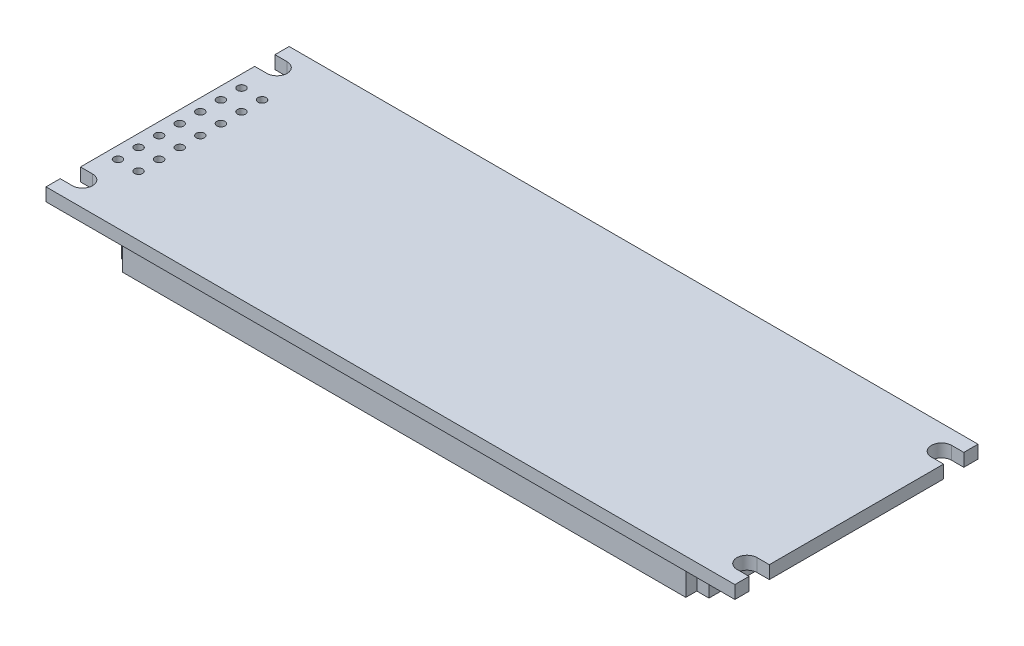
SolidWorks part; units mm, degrees
ref_plane "Plan de face" through (0, 0, 0) normal (0, 0, 1) x (1, 0, 0)
ref_plane "Plan de dessus" through (0, 0, 0) normal (0, 1, 0) x (1, 0, 0)
ref_plane "Plan de droite" through (0, 0, 0) normal (1, 0, 0) x (0, 0, -1)
sketch "Esquisse1" plane through (0, 0, 0) normal (0, 1, 0) x (1, 0, 0)
  line L0 (-41, -13.25) -> (-42.5, -13.25)
  line L1 (42.5, 15) -> (-42.5, 15)
  line L2 (-42.5, -10.75) -> (-42.5, 10.75)
  line L3 (42.5, -15) -> (-42.5, -15)
  line L4 (-42.5, -15) -> (-42.5, -13.25)
  line L5 (0, -15) -> (0, 15) construction
  line L6 (42.5, -15) -> (-42.5, 15) construction
  line L7 (-42.5, -10.75) -> (-41, -10.75)
  line L8 (-42.5, 0) -> (42.5, 0) construction
  line L10 (-42.5, 10.75) -> (-41, 10.75)
  line L11 (-42.5, 15) -> (-42.5, 13.25)
  line L12 (-41, 13.25) -> (-42.5, 13.25)
  line L13 (42.5, 15) -> (42.5, 13.25)
  line L14 (41, 13.25) -> (42.5, 13.25)
  line L15 (42.5, 10.75) -> (41, 10.75)
  line L16 (-42.5, 15) -> (42.5, -15) construction
  line L17 (42.5, -10.75) -> (41, -10.75)
  line L18 (42.5, -15) -> (42.5, -13.25)
  line L19 (41, -13.25) -> (42.5, -13.25)
  line L20 (42.5, -10.75) -> (42.5, 10.75)
  arc A0 (-41, -13.25) -> (-41, -10.75) centre (-41, -12) ccw
  arc A1 (-41, 13.25) -> (-41, 10.75) centre (-41, 12) cw
  arc A2 (41, 13.25) -> (41, 10.75) centre (41, 12) ccw
  arc A3 (41, -13.25) -> (41, -10.75) centre (41, -12) cw
  point P0 (0, 0)
  dimension "D1" = 85
  dimension "D3" = 82
  dimension "D5" = 1.25
  dimension "D2" = 30
  dimension "D4" = 24
extrude "Boss.-Extru.1" add sketch "Esquisse1" along normal blind 1.6 contours L19 L1 A1 L0 L3 L15 region at (0, 0, 0)
sketch "Esquisse2" plane through (0, 0, 0) normal (0, -1, 0) x (1, 0, 0)
  line L2 (42.5, 15) -> (-42.5, 15) construction
  line L3 (-42.5, 10.75) -> (-42.5, -10.75) construction
  circle A0 centre (-41, 7.62) radius 0.5
  circle A1 centre (-38.46, 7.62) radius 0.5
  circle A2 centre (-38.46, 5.08) radius 0.5
  circle A3 centre (-38.46, 2.54) radius 0.5
  circle A4 centre (-38.46, 0) radius 0.5
  circle A5 centre (-38.46, -2.54) radius 0.5
  circle A6 centre (-38.46, -5.08) radius 0.5
  circle A7 centre (-38.46, -7.62) radius 0.5
  circle A8 centre (-41, 5.08) radius 0.5
  circle A9 centre (-41, 2.54) radius 0.5
  circle A10 centre (-41, 0) radius 0.5
  circle A11 centre (-41, -2.54) radius 0.5
  circle A12 centre (-41, -5.08) radius 0.5
  circle A13 centre (-41, -7.62) radius 0.5
  dimension "D1" = 7.38
  dimension "D3" = 2
  dimension "D4" = 7
  dimension "D2" = 1.5
extrude "Enlèv. mat.-Extru.1" cut sketch "Esquisse2" against normal through all
sketch "Esquisse3" plane through (0, 0, 0) normal (0, -1, 0) x (1, 0, 0)
  line L0 (-34.75, 13.3) -> (-34.75, 11.95)
  line L1 (-34.75, 13.3) -> (34.75, 13.3)
  line L2 (36.25, 11.95) -> (36.25, -11.95)
  line L3 (34.75, -13.3) -> (-34.75, -13.3)
  line L4 (-36.25, -11.95) -> (-36.25, 11.95)
  line L7 (-34.75, 11.95) -> (-36.25, 11.95)
  line L11 (-34.75, -13.3) -> (-34.75, -11.95)
  line L12 (-34.75, -11.95) -> (-36.25, -11.95)
  line L13 (34.75, 13.3) -> (34.75, 11.95)
  line L14 (34.75, 11.95) -> (36.25, 11.95)
  line L15 (34.75, -11.95) -> (36.25, -11.95)
  line L16 (34.75, -13.3) -> (34.75, -11.95)
  point P0 (0, 0)
  point P1 (0, 0)
  point P7 (-36.25, 11.95)
  point P8 (-34.75, 13.3)
extrude "Boss.-Extru.2" add sketch "Esquisse3" along normal blind 4.5
sketch "Esquisse5" plane through (0, -4.5, 0) normal (0, -1, 0) x (1, 0, 0)
  line L1 (31, -8) -> (-31, -8)
  line L2 (31, -8) -> (31, 8)
  line L3 (31, 8) -> (-31, 8)
  line L4 (-31, -8) -> (-31, 8)
  line L5 (31, -8) -> (-31, 8) construction
  line L6 (31, 8) -> (-31, -8) construction
  point P0 (0, 0)
extrude "Enlèv. mat.-Extru.2" cut sketch "Esquisse5" against normal blind 0.2
sketch "Esquisse6" plane through (0, -4.3, 0) normal (0, -1, 0) x (1, 0, 0)
  line L1 (27.865, -5.49) -> (25.085, -5.49)
  line L2 (27.865, -5.49) -> (27.865, -0.6)
  line L3 (27.865, -0.6) -> (25.085, -0.6)
  line L4 (25.085, -5.49) -> (25.085, -0.6)
  line L5 (27.865, -5.49) -> (25.085, -0.6) construction
  line L6 (27.865, -0.6) -> (25.085, -5.49) construction
  line L7 (31, -8) -> (31, 8) construction
  line L8 (-31, -8) -> (31, -8) construction
  line L9 (24.385, -5.49) -> (21.605, -5.49)
  line L10 (24.385, -5.49) -> (24.385, -0.6)
  line L11 (24.385, -0.6) -> (21.605, -0.6)
  line L12 (21.605, -5.49) -> (21.605, -0.6)
  line L13 (20.905, -5.49) -> (18.125, -5.49)
  line L14 (20.905, -5.49) -> (20.905, -0.6)
  line L15 (20.905, -0.6) -> (18.125, -0.6)
  line L16 (18.125, -5.49) -> (18.125, -0.6)
  line L17 (17.425, -5.49) -> (14.645, -5.49)
  line L18 (17.425, -5.49) -> (17.425, -0.6)
  line L19 (17.425, -0.6) -> (14.645, -0.6)
  line L20 (14.645, -5.49) -> (14.645, -0.6)
  line L21 (13.945, -5.49) -> (11.165, -5.49)
  line L22 (13.945, -5.49) -> (13.945, -0.6)
  line L23 (13.945, -0.6) -> (11.165, -0.6)
  line L24 (11.165, -5.49) -> (11.165, -0.6)
  line L25 (10.465, -5.49) -> (7.685, -5.49)
  line L26 (10.465, -5.49) -> (10.465, -0.6)
  line L27 (10.465, -0.6) -> (7.685, -0.6)
  line L28 (7.685, -5.49) -> (7.685, -0.6)
  line L29 (6.985, -5.49) -> (4.205, -5.49)
  line L30 (6.985, -5.49) -> (6.985, -0.6)
  line L31 (6.985, -0.6) -> (4.205, -0.6)
  line L32 (4.205, -5.49) -> (4.205, -0.6)
  line L33 (3.505, -5.49) -> (0.725, -5.49)
  line L34 (3.505, -5.49) -> (3.505, -0.6)
  line L35 (3.505, -0.6) -> (0.725, -0.6)
  line L36 (0.725, -5.49) -> (0.725, -0.6)
  line L37 (0.025, -5.49) -> (-2.755, -5.49)
  line L38 (0.025, -5.49) -> (0.025, -0.6)
  line L39 (0.025, -0.6) -> (-2.755, -0.6)
  line L40 (-2.755, -5.49) -> (-2.755, -0.6)
  line L41 (-3.455, -5.49) -> (-6.235, -5.49)
  line L42 (-3.455, -5.49) -> (-3.455, -0.6)
  line L43 (-3.455, -0.6) -> (-6.235, -0.6)
  line L44 (-6.235, -5.49) -> (-6.235, -0.6)
  line L45 (-6.935, -5.49) -> (-9.715, -5.49)
  line L46 (-6.935, -5.49) -> (-6.935, -0.6)
  line L47 (-6.935, -0.6) -> (-9.715, -0.6)
  line L48 (-9.715, -5.49) -> (-9.715, -0.6)
  line L49 (-10.415, -5.49) -> (-13.195, -5.49)
  line L50 (-10.415, -5.49) -> (-10.415, -0.6)
  line L51 (-10.415, -0.6) -> (-13.195, -0.6)
  line L52 (-13.195, -5.49) -> (-13.195, -0.6)
  line L53 (-13.895, -5.49) -> (-16.675, -5.49)
  line L54 (-13.895, -5.49) -> (-13.895, -0.6)
  line L55 (-13.895, -0.6) -> (-16.675, -0.6)
  line L56 (-16.675, -5.49) -> (-16.675, -0.6)
  line L57 (-17.375, -5.49) -> (-20.155, -5.49)
  line L58 (-17.375, -5.49) -> (-17.375, -0.6)
  line L59 (-17.375, -0.6) -> (-20.155, -0.6)
  line L60 (-20.155, -5.49) -> (-20.155, -0.6)
  line L61 (-20.855, -5.49) -> (-23.635, -5.49)
  line L62 (-20.855, -5.49) -> (-20.855, -0.6)
  line L63 (-20.855, -0.6) -> (-23.635, -0.6)
  line L64 (-23.635, -5.49) -> (-23.635, -0.6)
  line L65 (-24.335, -5.49) -> (-27.115, -5.49)
  line L66 (-24.335, -5.49) -> (-24.335, -0.6)
  line L67 (-24.335, -0.6) -> (-27.115, -0.6)
  line L68 (-27.115, -5.49) -> (-27.115, -0.6)
  line L69 (27.865, 0.51) -> (25.085, 0.51)
  line L70 (27.865, 0.51) -> (27.865, 5.4)
  line L71 (27.865, 5.4) -> (25.085, 5.4)
  line L72 (25.085, 0.51) -> (25.085, 5.4)
  line L73 (24.385, 0.51) -> (21.605, 0.51)
  line L74 (24.385, 0.51) -> (24.385, 5.4)
  line L75 (24.385, 5.4) -> (21.605, 5.4)
  line L76 (21.605, 0.51) -> (21.605, 5.4)
  line L77 (20.905, 0.51) -> (18.125, 0.51)
  line L78 (20.905, 0.51) -> (20.905, 5.4)
  line L79 (20.905, 5.4) -> (18.125, 5.4)
  line L80 (18.125, 0.51) -> (18.125, 5.4)
  line L81 (17.425, 0.51) -> (14.645, 0.51)
  line L82 (17.425, 0.51) -> (17.425, 5.4)
  line L83 (17.425, 5.4) -> (14.645, 5.4)
  line L84 (14.645, 0.51) -> (14.645, 5.4)
  line L85 (13.945, 0.51) -> (11.165, 0.51)
  line L86 (13.945, 0.51) -> (13.945, 5.4)
  line L87 (13.945, 5.4) -> (11.165, 5.4)
  line L88 (11.165, 0.51) -> (11.165, 5.4)
  line L89 (10.465, 0.51) -> (7.685, 0.51)
  line L90 (10.465, 0.51) -> (10.465, 5.4)
  line L91 (10.465, 5.4) -> (7.685, 5.4)
  line L92 (7.685, 0.51) -> (7.685, 5.4)
  line L93 (6.985, 0.51) -> (4.205, 0.51)
  line L94 (6.985, 0.51) -> (6.985, 5.4)
  line L95 (6.985, 5.4) -> (4.205, 5.4)
  line L96 (4.205, 0.51) -> (4.205, 5.4)
  line L97 (3.505, 0.51) -> (0.725, 0.51)
  line L98 (3.505, 0.51) -> (3.505, 5.4)
  line L99 (3.505, 5.4) -> (0.725, 5.4)
  line L100 (0.725, 0.51) -> (0.725, 5.4)
  line L101 (0.025, 0.51) -> (-2.755, 0.51)
  line L102 (0.025, 0.51) -> (0.025, 5.4)
  line L103 (0.025, 5.4) -> (-2.755, 5.4)
  line L104 (-2.755, 0.51) -> (-2.755, 5.4)
  line L105 (-3.455, 0.51) -> (-6.235, 0.51)
  line L106 (-3.455, 0.51) -> (-3.455, 5.4)
  line L107 (-3.455, 5.4) -> (-6.235, 5.4)
  line L108 (-6.235, 0.51) -> (-6.235, 5.4)
  line L109 (-6.935, 0.51) -> (-9.715, 0.51)
  line L110 (-6.935, 0.51) -> (-6.935, 5.4)
  line L111 (-6.935, 5.4) -> (-9.715, 5.4)
  line L112 (-9.715, 0.51) -> (-9.715, 5.4)
  line L113 (-10.415, 0.51) -> (-13.195, 0.51)
  line L114 (-10.415, 0.51) -> (-10.415, 5.4)
  line L115 (-10.415, 5.4) -> (-13.195, 5.4)
  line L116 (-13.195, 0.51) -> (-13.195, 5.4)
  line L117 (-13.895, 0.51) -> (-16.675, 0.51)
  line L118 (-13.895, 0.51) -> (-13.895, 5.4)
  line L119 (-13.895, 5.4) -> (-16.675, 5.4)
  line L120 (-16.675, 0.51) -> (-16.675, 5.4)
  line L121 (-17.375, 0.51) -> (-20.155, 0.51)
  line L122 (-17.375, 0.51) -> (-17.375, 5.4)
  line L123 (-17.375, 5.4) -> (-20.155, 5.4)
  line L124 (-20.155, 0.51) -> (-20.155, 5.4)
  line L125 (-20.855, 0.51) -> (-23.635, 0.51)
  line L126 (-20.855, 0.51) -> (-20.855, 5.4)
  line L127 (-20.855, 5.4) -> (-23.635, 5.4)
  line L128 (-23.635, 0.51) -> (-23.635, 5.4)
  line L129 (-24.335, 0.51) -> (-27.115, 0.51)
  line L130 (-24.335, 0.51) -> (-24.335, 5.4)
  line L131 (-24.335, 5.4) -> (-27.115, 5.4)
  line L132 (-27.115, 0.51) -> (-27.115, 5.4)
  point P0 (26.475, -3.045)
  dimension "D1" = 3.135
  dimension "D2" = 2.51
  dimension "D3" = 16
  dimension "D4" = 2
extrude "Enlèv. mat.-Extru.3" cut sketch "Esquisse6" against normal blind 0.1
